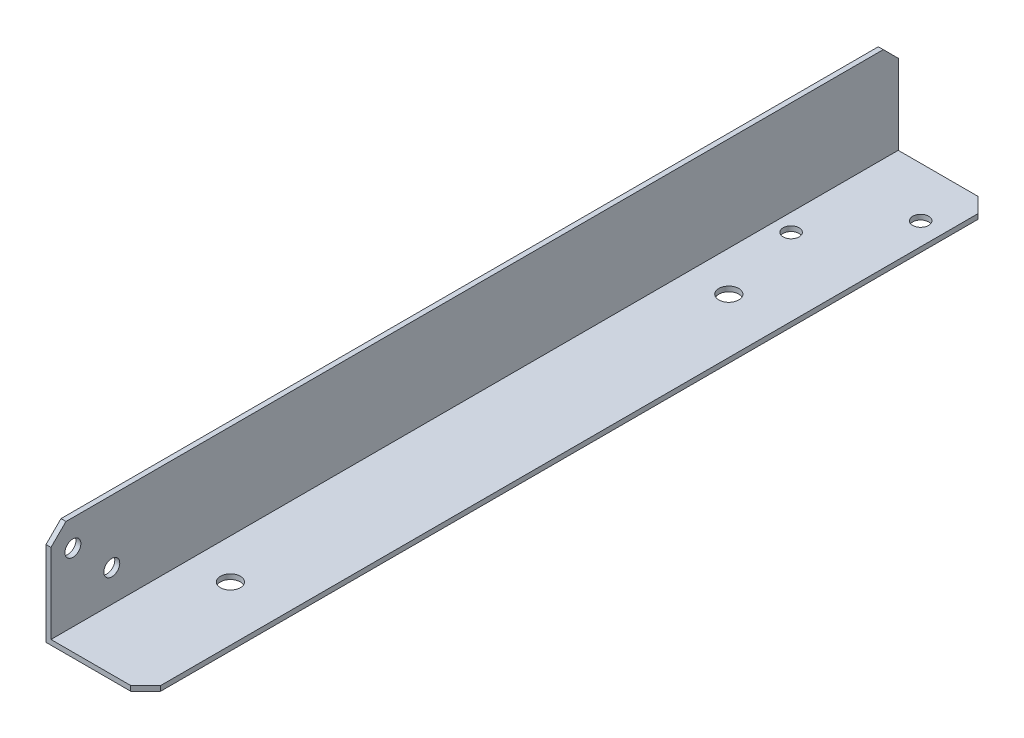
SolidWorks part; units mm, degrees
material "6063-T5"
ref_plane "Спереди" through (0, 0, 0) normal (0, 0, 1) x (1, 0, 0)
ref_plane "Сверху" through (0, 0, 0) normal (0, 1, 0) x (1, 0, 0)
ref_plane "Справа" through (0, 0, 0) normal (1, 0, 0) x (0, 0, -1)
sketch "Sketch1" plane through (0, 0, 0) normal (0, 0, 1) x (1, 0, 0)
  line L0 (0, 0) -> (20, 0)
  line L1 (20, 0) -> (20, 1)
  line L2 (20, 1) -> (1, 1)
  line L3 (1, 1) -> (1, 20)
  line L4 (1, 20) -> (0, 20)
  line L5 (0, 20) -> (0, 0)
  dimension "D1" = 20
  dimension "D2" = 20
  dimension "D3" = 1
  dimension "D4" = 1
extrude "Base" add sketch "Sketch1" along normal blind 170
chamfer "ChamferEdges" distance 3 angle 45 4 edges at (20, 0.5, 170) (0.5, 20, 170) (0.5, 20, 0) (20, 0.5, 0)
hole_wizard "Ø4.0 (4) Cable tie Holes" positions "Sketch8" profile "Sketch9" hole size "Ø4.0" standard "ANSI Metric" end condition through all
sketch "Sketch8" plane through (0, 1, 0) normal (0, 1, 0) x (1, 0, 0)
  line L0 (0, -167) -> (0, -3) construction
  line L1 (17, 0) -> (1, 0) construction
  point P0 (9, -42)
  point P2 (9, -142)
  dimension "D1" = 9
  dimension "D2" = 42
  dimension "D3" = 142
sketch "Sketch9" plane through (9, 1, 42) normal (1, 0, 0) x (0, 0, 1)
  line L0 (0, 0) -> (0, 1)
  line L1 (0, 1) -> (2, 1)
  line L2 (2, 1) -> (2, 0)
  line L5 (2, 0) -> (0, 0)
  line L11 (0, -6.35) -> (0, 107.95) construction
  dimension "Thru Hole Dia." = 4
  dimension "Thru Hole Depth" = 1
hole_wizard "Ø3.1 (3.1) CableChainSideHoles" positions "Sketch10" profile "Sketch11" hole size "Ø3.2" standard "ANSI Metric" end condition through all
sketch "Sketch10" plane through (1, 0, 0) normal (1, 0, 0) x (0, 0, -1)
  line L0 (-167, 0) -> (-3, 0) construction
  line L1 (-170, 1) -> (-170, 17) construction
  point P0 (-165.6, 14.68)
  point P2 (-157.8, 7.38)
  dimension "D1" = 7.3
  dimension "D2" = 7.8
  dimension "D3" = 7.38
  dimension "D4" = 4.4
sketch "Sketch11" plane through (1, 14.68, 165.6) normal (0, 1, 0) x (0, 0, -1)
  line L0 (0, 0) -> (0, 1)
  line L1 (0, 1) -> (1.6, 1)
  line L2 (1.6, 1) -> (1.6, 0)
  line L5 (1.6, 0) -> (0, 0)
  line L11 (0, -6.35) -> (0, 107.95) construction
  dimension "Thru Hole Dia." = 3.2
  dimension "Thru Hole Depth" = 1
hole_wizard "Ø3.2 (3.2) CarriageSide" positions "Sketch12" profile "Sketch13" hole size "Ø3.2" standard "ANSI Metric" end condition through all
sketch "Sketch12" plane through (0, 1, 0) normal (0, 1, 0) x (1, 0, 0)
  line L0 (0, -167) -> (0, -3) construction
  line L1 (17, 0) -> (1, 0) construction
  point P0 (15.5, -10)
  point P2 (4.5, -25)
  dimension "D1" = 4.5
  dimension "D2" = 15
  dimension "D3" = 10
  dimension "D4" = 11
sketch "Sketch13" plane through (15.5, 1, 10) normal (1, 0, 0) x (0, 0, 1)
  line L0 (0, 0) -> (0, 1)
  line L1 (0, 1) -> (1.6, 1)
  line L2 (1.6, 1) -> (1.6, 0)
  line L5 (1.6, 0) -> (0, 0)
  line L11 (0, -6.35) -> (0, 107.95) construction
  dimension "Thru Hole Dia." = 3.2
  dimension "Thru Hole Depth" = 1
equation "\"D2@Sketch1\"=\"D1@Sketch1\""
equation "\"D4@Sketch1\"=\"D3@Sketch1\""
